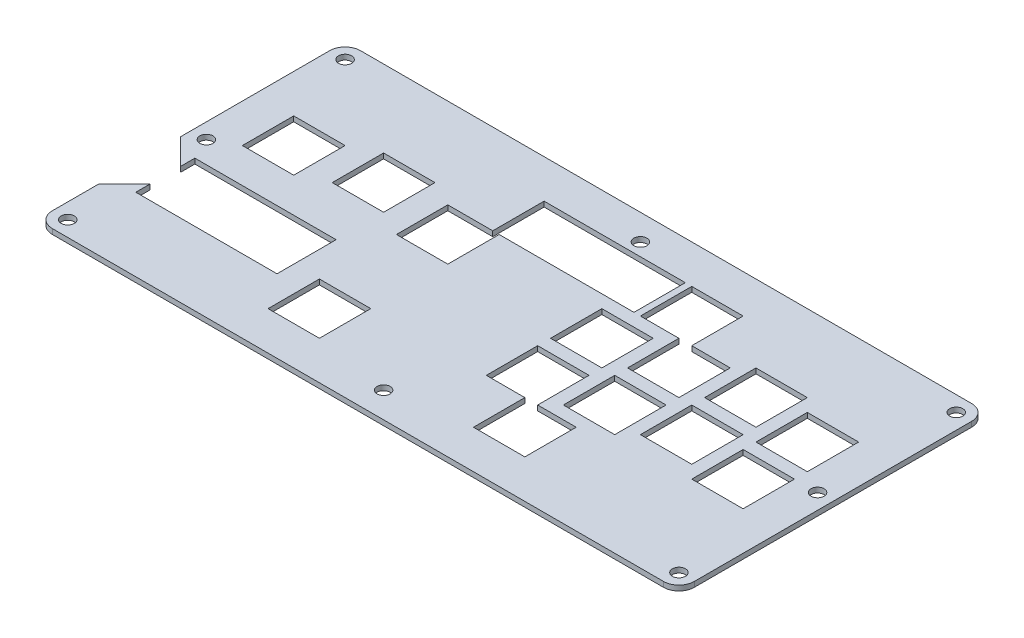
SolidWorks part; units mm, degrees
ref_plane "前视基准面" through (0, 0, 0) normal (0, 0, 1) x (1, 0, 0)
ref_plane "上视基准面" through (0, 0, 0) normal (0, 1, 0) x (1, 0, 0)
ref_plane "右视基准面" through (0, 0, 0) normal (1, 0, 0) x (0, 0, -1)
sketch "草图1" plane through (0, 0, 0) normal (0, 1, 0) x (1, 0, 0)
  line L0 (11.1275, 62.0332) -> (11.1275, 120.0332)
  line L1 (17.1275, 126.0332) -> (255.1275, 126.0332)
  line L2 (261.1275, 120.0332) -> (261.1275, 12.0332)
  line L3 (255.1275, 6.0332) -> (17.1275, 6.0332)
  line L4 (11.1275, 12.0332) -> (11.1275, 30.0332)
  line L5 (21.1275, 40.0332) -> (21.1275, 34.5332)
  line L6 (21.1275, 34.5332) -> (76.1275, 34.5332)
  line L7 (76.1275, 34.5332) -> (76.1275, 57.5332)
  line L8 (76.1275, 57.5332) -> (21.1275, 57.5332)
  line L9 (21.1275, 57.5332) -> (21.1275, 52.0332)
  line L10 (21.1275, 52.0332) -> (11.1275, 62.0332)
  line L11 (21.1275, 40.0332) -> (11.1275, 30.0332)
  line L12 (56.1275, 96.0332) -> (76.1275, 96.0332)
  line L13 (76.1275, 96.0332) -> (76.1275, 76.0332)
  line L14 (76.1275, 76.0332) -> (56.1275, 76.0332)
  line L15 (56.1275, 76.0332) -> (56.1275, 96.0332)
  line L16 (106.1275, 91.0332) -> (106.1275, 71.0332)
  line L17 (106.1275, 71.0332) -> (86.1275, 71.0332)
  line L18 (86.1275, 71.0332) -> (86.1275, 91.0332)
  line L19 (86.1275, 91.0332) -> (103.6275, 91.0332)
  line L20 (86.1275, 41.0332) -> (106.1275, 41.0332)
  line L21 (106.1275, 41.0332) -> (106.1275, 21.0332)
  line L22 (106.1275, 21.0332) -> (86.1275, 21.0332)
  line L23 (86.1275, 21.0332) -> (86.1275, 41.0332)
  line L24 (26.1275, 91.0332) -> (46.1275, 91.0332)
  line L25 (46.1275, 91.0332) -> (46.1275, 71.0332)
  line L26 (46.1275, 71.0332) -> (26.1275, 71.0332)
  line L27 (26.1275, 71.0332) -> (26.1275, 91.0332)
  line L28 (176.1275, 91.0332) -> (161.1275, 91.0332)
  line L29 (161.1275, 91.0332) -> (161.1275, 111.0332)
  line L30 (161.1275, 111.0332) -> (181.1275, 111.0332)
  line L31 (181.1275, 111.0332) -> (181.1275, 91.0332)
  line L32 (151.1275, 86.0332) -> (171.1275, 86.0332)
  line L33 (171.1275, 86.0332) -> (171.1275, 66.0332)
  line L34 (171.1275, 66.0332) -> (151.1275, 66.0332)
  line L35 (151.1275, 66.0332) -> (151.1275, 86.0332)
  line L36 (181.1275, 91.0332) -> (196.1275, 91.0332)
  line L37 (196.1275, 91.0332) -> (196.1275, 71.0332)
  line L38 (196.1275, 71.0332) -> (176.1275, 71.0332)
  line L39 (176.1275, 71.0332) -> (176.1275, 91.0332)
  line L40 (201.1275, 96.0332) -> (221.1275, 96.0332)
  line L41 (221.1275, 96.0332) -> (221.1275, 76.0332)
  line L42 (221.1275, 76.0332) -> (201.1275, 76.0332)
  line L43 (201.1275, 76.0332) -> (201.1275, 96.0332)
  line L44 (226.1275, 91.0332) -> (246.1275, 91.0332)
  line L45 (246.1275, 91.0332) -> (246.1275, 71.0332)
  line L46 (246.1275, 71.0332) -> (226.1275, 71.0332)
  line L47 (226.1275, 71.0332) -> (226.1275, 91.0332)
  line L48 (166.1275, 41.0332) -> (151.1275, 41.0332)
  line L49 (151.1275, 41.0332) -> (151.1275, 61.0332)
  line L50 (151.1275, 61.0332) -> (171.1275, 61.0332)
  line L51 (171.1275, 61.0332) -> (171.1275, 41.0332)
  line L52 (176.1275, 66.0332) -> (196.1275, 66.0332)
  line L53 (196.1275, 66.0332) -> (196.1275, 46.0332)
  line L54 (196.1275, 46.0332) -> (176.1275, 46.0332)
  line L55 (176.1275, 46.0332) -> (176.1275, 66.0332)
  line L56 (201.1275, 71.0332) -> (221.1275, 71.0332)
  line L57 (221.1275, 71.0332) -> (221.1275, 51.0332)
  line L58 (221.1275, 51.0332) -> (201.1275, 51.0332)
  line L59 (201.1275, 51.0332) -> (201.1275, 71.0332)
  line L60 (226.1275, 66.0332) -> (246.1275, 66.0332)
  line L61 (246.1275, 66.0332) -> (246.1275, 46.0332)
  line L62 (246.1275, 46.0332) -> (226.1275, 46.0332)
  line L63 (226.1275, 46.0332) -> (226.1275, 66.0332)
  line L64 (171.1275, 41.0332) -> (186.1275, 41.0332)
  line L65 (186.1275, 41.0332) -> (186.1275, 21.0332)
  line L66 (186.1275, 21.0332) -> (166.1275, 21.0332)
  line L67 (166.1275, 21.0332) -> (166.1275, 41.0332)
  line L68 (103.6275, 91.0332) -> (103.6275, 104.0332)
  line L69 (158.6275, 111.0332) -> (158.6275, 91.0332)
  line L70 (103.6275, 111.0332) -> (158.6275, 111.0332)
  line L71 (158.6275, 91.0332) -> (106.1275, 91.0332)
  line L72 (103.6275, 104.0332) -> (103.6275, 111.0332)
  arc A0 (17.1275, 126.0332) -> (11.1275, 120.0332) centre (17.1275, 120.0332) ccw
  arc A1 (261.1275, 120.0332) -> (255.1275, 126.0332) centre (255.1275, 120.0332) ccw
  arc A2 (255.1275, 6.0332) -> (261.1275, 12.0332) centre (255.1275, 12.0332) ccw
  arc A3 (11.1275, 12.0332) -> (17.1275, 6.0332) centre (17.1275, 12.0332) ccw
  circle A4 centre (17.1275, 120.0332) radius 2.55
  circle A5 centre (255.1275, 120.0332) radius 2.55
  circle A6 centre (136.1275, 116.0332) radius 2.55
  circle A7 centre (17.1275, 12.0332) radius 2.55
  circle A8 centre (255.1275, 12.0332) radius 2.55
  circle A9 centre (136.1275, 16.0332) radius 2.55
  circle A10 centre (255.1275, 66.0332) radius 2.55
  circle A11 centre (17.1275, 66.0332) radius 2.55
  circle A12 centre (136.1275, 116.0332) radius 2.55
extrude "凸台-拉伸1" add sketch "草图1" along normal blind 2 contours L4 A3 L3 A2 L2 A1 L1 A0 L0 L10 L9 L8 L7 L6 L5 L11 A11 A10 A9 A8 A7 A6 A5 A4 L68 L72 L70 L69 L71 L16 L17 L18 L19 L66 L67 L48 L49 L50 L51 L64 L65 region at (136.7174, 0, -64.9787)
